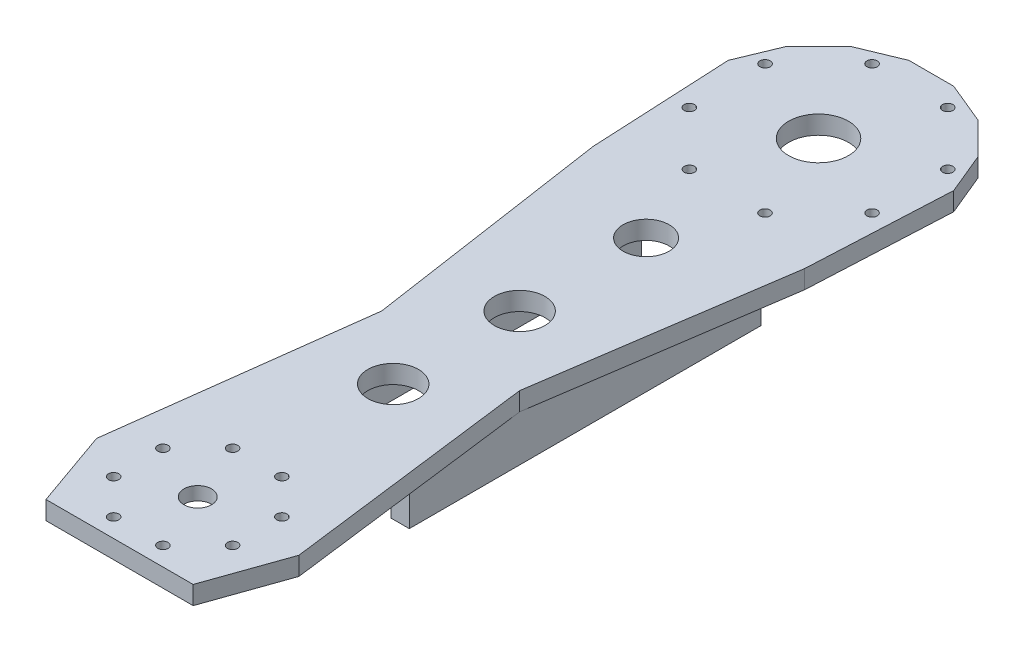
SolidWorks part; units mm, degrees
ref_plane "Front Plane" through (0, 0, 0) normal (0, 0, 1) x (1, 0, 0)
ref_plane "Top Plane" through (0, 0, 0) normal (0, 1, 0) x (1, 0, 0)
ref_plane "Right Plane" through (0, 0, 0) normal (1, 0, 0) x (0, 0, -1)
ref_plane "PL_Thigh_Plate_base" through (0, 36, 0) normal (0, 1, 0) x (1, 0, 0)
sketch "SK_Thigh_Plate" plane through (0, 36, 0) normal (0, 1, 0) x (1, 0, 0)
  line L0 (-32, -34) -> (32, -34)
  line L1 (32, -34) -> (44, 0)
  line L2 (44, 0) -> (30, 110)
  line L3 (30, 110) -> (46, 218)
  line L4 (46, 218) -> (49.0393, 279.7545)
  line L5 (49.0393, 279.7545) -> (41.5735, 297.7785)
  line L6 (41.5735, 297.7785) -> (27.7785, 311.5735)
  line L7 (27.7785, 311.5735) -> (9.7545, 319.0393)
  line L8 (9.7545, 319.0393) -> (-9.7545, 319.0393)
  line L9 (-9.7545, 319.0393) -> (-27.7785, 311.5735)
  line L10 (-27.7785, 311.5735) -> (-41.5735, 297.7785)
  line L11 (-41.5735, 297.7785) -> (-49.0393, 279.7545)
  line L12 (-49.0393, 279.7545) -> (-46, 218)
  line L13 (-46, 218) -> (-30, 110)
  line L14 (-30, 110) -> (-44, 0)
  line L15 (-44, 0) -> (-32, -34)
  circle A0 centre (25.8686, 10.7151) radius 2.25
  circle A1 centre (10.7151, 25.8686) radius 2.25
  circle A2 centre (-10.7151, 25.8686) radius 2.25
  circle A3 centre (-25.8686, 10.7151) radius 2.25
  circle A4 centre (-25.8686, -10.7151) radius 2.25
  circle A5 centre (-10.7151, -25.8686) radius 2.25
  circle A6 centre (10.7151, -25.8686) radius 2.25
  circle A7 centre (25.8686, -10.7151) radius 2.25
  circle A8 centre (39.7268, 286.4554) radius 2.25
  circle A9 centre (16.4554, 309.7268) radius 2.25
  circle A10 centre (-16.4554, 309.7268) radius 2.25
  circle A11 centre (-39.7268, 286.4554) radius 2.25
  circle A12 centre (-39.7268, 253.5446) radius 2.25
  circle A13 centre (-16.4554, 230.2732) radius 2.25
  circle A14 centre (16.4554, 230.2732) radius 2.25
  circle A15 centre (39.7268, 253.5446) radius 2.25
  circle A16 centre (0, 0) radius 6
  circle A17 centre (0, 270) radius 13
  circle A18 centre (0, 85) radius 11
  circle A19 centre (0, 140) radius 11
  circle A20 centre (0, 195) radius 10
  dimension "D31_SK_Thigh_Plate" = 4.5
  dimension "D34_SK_Thigh_Plate" = 4.5
  dimension "D37_SK_Thigh_Plate" = 4.5
  dimension "D40_SK_Thigh_Plate" = 4.5
  dimension "D43_SK_Thigh_Plate" = 4.5
  dimension "D46_SK_Thigh_Plate" = 4.5
  dimension "D49_SK_Thigh_Plate" = 4.5
  dimension "D52_SK_Thigh_Plate" = 4.5
  dimension "D55_SK_Thigh_Plate" = 4.5
  dimension "D58_SK_Thigh_Plate" = 4.5
  dimension "D61_SK_Thigh_Plate" = 4.5
  dimension "D64_SK_Thigh_Plate" = 4.5
  dimension "D67_SK_Thigh_Plate" = 4.5
  dimension "D70_SK_Thigh_Plate" = 4.5
  dimension "D73_SK_Thigh_Plate" = 4.5
  dimension "D76_SK_Thigh_Plate" = 4.5
  dimension "D79_SK_Thigh_Plate" = 12
  dimension "D80_SK_Thigh_Plate" = 26
  dimension "D82_SK_Thigh_Plate" = 22
  dimension "D84_SK_Thigh_Plate" = 22
  dimension "D86_SK_Thigh_Plate" = 20
  dimension "P1" = 32
  dimension "P2" = 34
  dimension "P3" = 32
  dimension "P4" = 34
  dimension "P5" = 44
  dimension "P6" = 30
  dimension "P7" = 110
  dimension "P8" = 46
  dimension "P9" = 218
  dimension "P10" = 49.0393
  dimension "P11" = 279.7545
  dimension "P12" = 41.5735
  dimension "P13" = 297.7785
  dimension "P14" = 27.7785
  dimension "P15" = 311.5735
  dimension "P16" = 9.7545
  dimension "P17" = 319.0393
  dimension "P18" = 9.7545
  dimension "P19" = 319.0393
  dimension "P20" = 27.7785
  dimension "P21" = 311.5735
  dimension "P22" = 41.5735
  dimension "P23" = 297.7785
  dimension "P24" = 49.0393
  dimension "P25" = 279.7545
  dimension "P26" = 46
  dimension "P27" = 218
  dimension "P28" = 30
  dimension "P29" = 110
  dimension "P30" = 44
  dimension "P32" = 25.8686
  dimension "P33" = 10.7151
  dimension "P35" = 10.7151
  dimension "P36" = 25.8686
  dimension "P38" = 10.7151
  dimension "P39" = 25.8686
  dimension "P41" = 25.8686
  dimension "P42" = 10.7151
  dimension "P44" = 25.8686
  dimension "P45" = 10.7151
  dimension "P47" = 10.7151
  dimension "P48" = 25.8686
  dimension "P50" = 10.7151
  dimension "P51" = 25.8686
  dimension "P53" = 25.8686
  dimension "P54" = 10.7151
  dimension "P56" = 39.7268
  dimension "P57" = 286.4554
  dimension "P59" = 16.4554
  dimension "P60" = 309.7268
  dimension "P62" = 16.4554
  dimension "P63" = 309.7268
  dimension "P65" = 39.7268
  dimension "P66" = 286.4554
  dimension "P68" = 39.7268
  dimension "P69" = 253.5446
  dimension "P71" = 16.4554
  dimension "P72" = 230.2732
  dimension "P74" = 16.4554
  dimension "P75" = 230.2732
  dimension "P77" = 39.7268
  dimension "P78" = 253.5446
  dimension "P81" = 270
  dimension "P83" = 85
  dimension "P85" = 140
  dimension "P87" = 195
extrude "Thigh_Plate" add sketch "SK_Thigh_Plate" along normal blind 8
ref_plane "PL_Pitch_Pilot_Recess_base" through (0, 36, 0) normal (0, 1, 0) x (1, 0, 0)
sketch "SK_Pitch_Pilot_Recess" plane through (0, 36, 0) normal (0, 1, 0) x (1, 0, 0)
  circle A0 centre (0, 0) radius 22.15
  dimension "D1_SK_Pitch_Pilot_Recess" = 44.3
extrude "Pitch_Pilot_Recess" cut sketch "SK_Pitch_Pilot_Recess" along normal blind 2.2
ref_plane "PL_Front_Flange_base" through (22, 0, 0) normal (1, 0, 0) x (0, 0, -1)
sketch "SK_Front_Flange" plane through (22, 0, 0) normal (1, 0, 0) x (0, 0, -1)
  line L0 (215, 16) -> (215, 36)
  line L1 (215, 36) -> (62, 36)
  line L2 (62, 36) -> (62, 16)
  line L3 (62, 16) -> (215, 16)
  dimension "P1" = 215
  dimension "P2" = 16
  dimension "P3" = 215
  dimension "P4" = 36
  dimension "P5" = 62
  dimension "P6" = 36
  dimension "P7" = 62
  dimension "P8" = 16
extrude "Front_Flange" add sketch "SK_Front_Flange" along normal blind 8
ref_plane "PL_Back_Flange_base" through (-30, 0, 0) normal (1, 0, 0) x (0, 0, -1)
sketch "SK_Back_Flange" plane through (-30, 0, 0) normal (1, 0, 0) x (0, 0, -1)
  line L0 (215, 16) -> (215, 36)
  line L1 (215, 36) -> (62, 36)
  line L2 (62, 36) -> (62, 16)
  line L3 (62, 16) -> (215, 16)
  dimension "P1" = 215
  dimension "P2" = 16
  dimension "P3" = 215
  dimension "P4" = 36
  dimension "P5" = 62
  dimension "P6" = 36
  dimension "P7" = 62
  dimension "P8" = 16
extrude "Back_Flange" add sketch "SK_Back_Flange" along normal blind 8
ref_axis "AX_PitchY" through (0, 45.4, 0) along (0, -1, 0)
ref_plane "PL_PitchRef" through (0, 0, 0) normal (-0.6428, 0, 0.766) x (0, -1, 0)
equation "\"Thigh_length\" = 270"
equation "\"Thigh_plate_t\" = 8"
